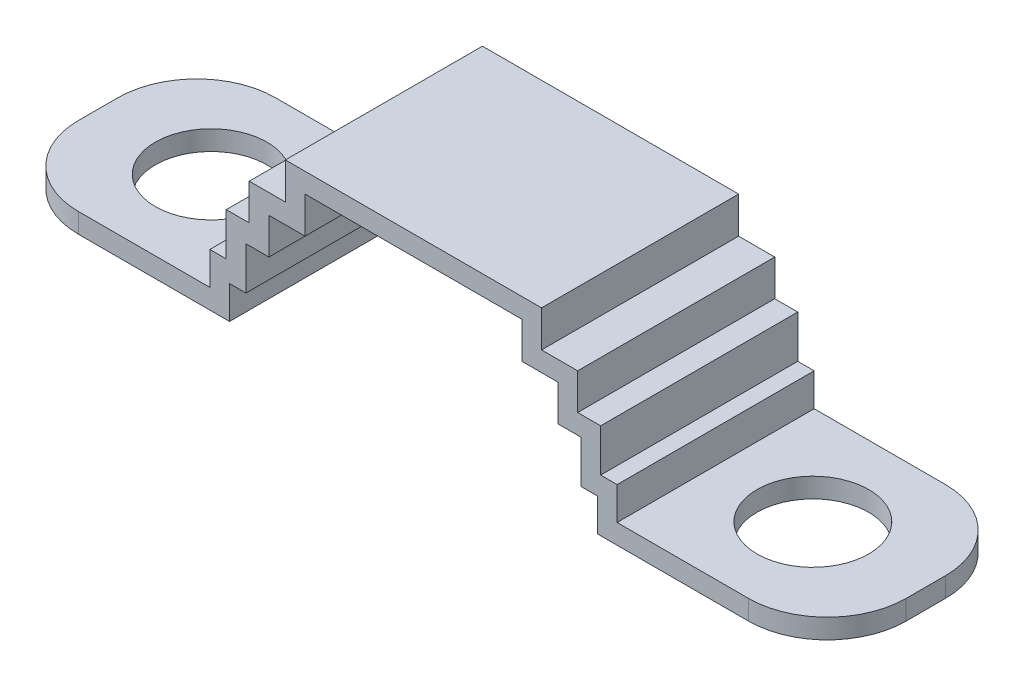
SolidWorks part; units mm, degrees
material "PBT General Purpose"
ref_plane "Front Plane" through (0, 0, 0) normal (0, 0, 1) x (1, 0, 0)
ref_plane "Top Plane" through (0, 0, 0) normal (0, 1, 0) x (1, 0, 0)
ref_plane "Right Plane" through (0, 0, 0) normal (1, 0, 0) x (0, 0, -1)
sketch "Sketch1" plane through (0, 0, 0) normal (0, 0, 1) x (1, 0, 0)
  line L0 (-63, 4.5) -> (-28, 4.5)
  line L1 (-28, 4.5) -> (-28, 9.5)
  line L2 (-28, 9.5) -> (-25.5, 9.5)
  line L3 (-25.5, 9.5) -> (-25.5, 16)
  line L4 (-25.5, 16) -> (-22, 16)
  line L5 (-22, 16) -> (-22, 21.5)
  line L6 (-22, 21.5) -> (-16.5, 21.5)
  line L7 (-16.5, 21.5) -> (-16.5, 27.05)
  line L8 (-16.5, 27.05) -> (0, 27.05)
  circle A0 centre (0, 0) radius 27.05
  dimension "D1" = 54.1
  dimension "D2" = 35
  dimension "D3" = 4.5
  dimension "D4" = 28
  dimension "D5" = 5
  dimension "D6" = 2.5
  dimension "D7" = 6.5
  dimension "D8" = 3.5
  dimension "D9" = 5.5
  dimension "D10" = 5.5
  dimension "D11" = 16.5
  dimension "D12" = 5.55
extrude "Extrude-Thin1" add sketch "Sketch1" along normal mid plane 30 thin contours L0 L1 L2 L3 L4 L5 L6 L7 L8 thin type one direction reverse wall 3
sketch "Sketch2" plane through (0, 7.5, 0) normal (0, 1, 0) x (1, 0, 0)
  line L0 (0, -15) -> (0, 15) construction
  circle A0 centre (-45.8, 0) radius 8.5
  dimension "D1" = 17
  dimension "D2" = 45.8
extrude "Cut-Extrude1" cut sketch "Sketch2" against normal through all
fillet "Fillet1" radius 12 2 edges at (-63, 6, -15) (-63, 6, 15)
mirror "Mirror1" about plane through (0, 30.05, 15) normal (1, 0, 0) of "Fillet1", "Cut-Extrude1", "Extrude-Thin1"
